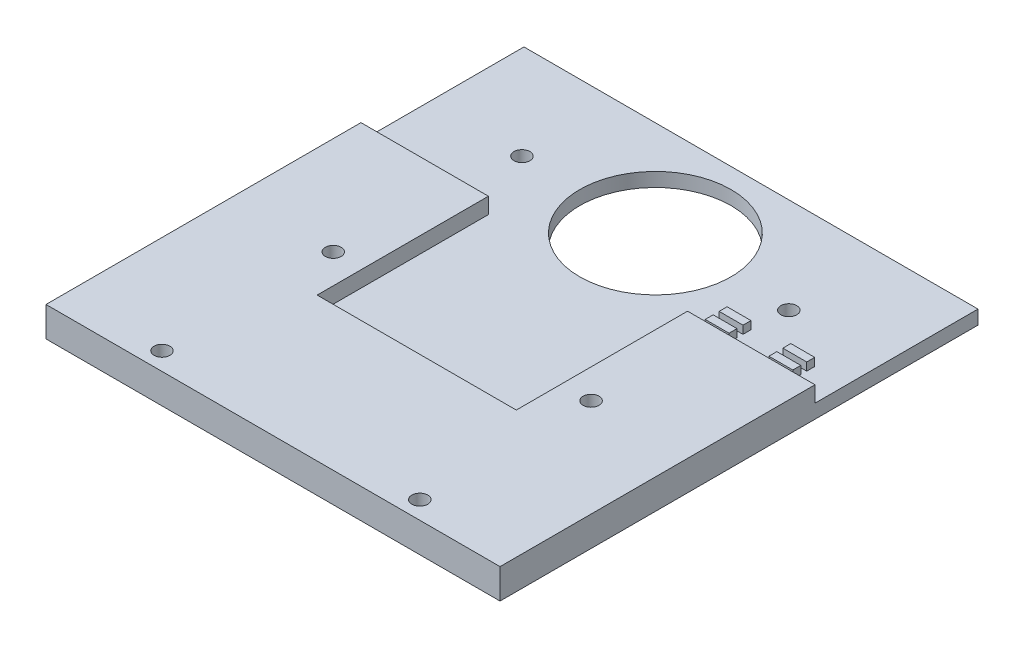
SolidWorks part; units mm, degrees
ref_plane "Ebene vorne" through (0, 0, 0) normal (0, 0, 1) x (1, 0, 0)
ref_plane "Ebene oben" through (0, 0, 0) normal (0, 1, 0) x (1, 0, 0)
ref_plane "Ebene rechts" through (0, 0, 0) normal (1, 0, 0) x (0, 0, -1)
sketch "Skizze1" plane through (0, 0, 0) normal (0, 1, 0) x (1, 0, 0)
  line L1 (0, 0) -> (57, 0)
  line L2 (0, 0) -> (0, 60)
  line L3 (0, 60) -> (57, 60)
  line L4 (57, 0) -> (57, 60)
  dimension "D1" = 57
  dimension "D2" = 60
extrude "Aufsatz-Linear austragen1" add sketch "Skizze1" against normal blind 1.75
sketch "Skizze3" plane through (0, 0, 0) normal (0, 1, 0) x (1, 0, 0)
  line L0 (57, 60) -> (0, 60) construction
  line L2 (57, 0) -> (57, 60) construction
  circle A0 centre (28.5, 48) radius 9.4954
  dimension "D1" = 12
  dimension "D2" = 28.5
extrude "Schnitt-Linear austragen1" cut sketch "Skizze3" against normal blind 2
sketch "Skizze4" plane through (0, 0, 0) normal (0, 1, 0) x (1, 0, 0)
  line L0 (0, 60) -> (0, 0) construction
  line L1 (57, 0) -> (0, 0)
  line L2 (57, 0) -> (57, 39.5386)
  line L3 (57, 39.5386) -> (0, 39.5386)
  line L4 (0, 0) -> (0, 39.5386)
extrude "Aufsatz-Linear austragen2" add sketch "Skizze4" along normal blind 2
sketch "Skizze5" plane through (0, 2, 0) normal (0, 1, 0) x (1, 0, 0)
  circle A0 centre (12.3153, 23.7449) radius 1
  circle A1 centre (12.3153, 2.2449) radius 1
  dimension "D1" = 2
  dimension "D2" = 2
extrude "Schnitt-Linear austragen2" cut sketch "Skizze5" against normal blind 4
ref_plane "Ebene1" through (28.5, 0, 0) normal (-1, 0, 0) x (0, 0, 1)
mirror "Spiegeln1" about plane through (28.5, 0, 0) normal (-1, 0, 0) of "Schnitt-Linear austragen2"
sketch "Skizze10" plane through (0, 0, 0) normal (0, 1, 0) x (1, 0, 0)
  line L1 (57, 60) -> (0, 60) construction
  line L2 (57, 39.5386) -> (57, 60) construction
  line L3 (0, 60) -> (0, 39.5386) construction
  circle A0 centre (45.25, 48) radius 1
  circle A1 centre (11.75, 48) radius 1
  dimension "D1" = 12
  dimension "D2" = 12
  dimension "D3" = 11.75
  dimension "D4" = 11.75
extrude "Schnitt-Linear austragen3" cut sketch "Skizze10" against normal blind 2
sketch "Skizze13" plane through (0, 0, 0) normal (0, 1, 0) x (1, 0, 0)
  line L0 (53, 42.5) -> (50, 42.5)
  line L1 (50, 42.5) -> (50, 43.5)
  line L2 (50, 43.5) -> (53, 43.5)
  line L5 (45, 42.5) -> (45, 43.5)
  line L6 (45, 43.5) -> (42, 43.5)
  line L7 (42, 43.5) -> (42, 42.5)
  line L8 (42, 42.5) -> (45, 42.5)
  line L9 (53, 40.75) -> (50, 40.75)
  line L10 (50, 40.75) -> (50, 41.75)
  line L11 (50, 41.75) -> (53, 41.75)
  line L12 (53, 41.75) -> (53, 40.75)
  line L14 (45, 41.75) -> (42, 41.75)
  line L15 (42, 41.75) -> (42, 40.75)
  line L16 (42, 40.75) -> (45, 40.75)
  line L17 (45, 40.75) -> (45, 41.75)
  line L18 (57, 60) -> (0, 60) construction
  line L19 (57, 39.5386) -> (57, 60) construction
  line L20 (53, 42.5) -> (53, 43.5)
  dimension "D1" = 0.75
  dimension "D2" = 1
  dimension "D3" = 1
  dimension "D4" = 0.75
  dimension "D5" = 16.5
  dimension "D6" = 16.5
  dimension "D7" = 4
  dimension "D8" = 1
  dimension "D9" = 3
  dimension "D10" = 1
  dimension "D11" = 3
  dimension "D12" = 3
  dimension "D13" = 16.5
extrude "Aufsatz-Linear austragen6" add sketch "Skizze13" along normal blind 1
ref_plane "Ebene2" through (0, 0, -22) normal (0, 0, -1) x (-1, 0, 0)
sketch "Skizze14" plane through (0, 2, 0) normal (0, 1, 0) x (1, 0, 0)
  line L0 (16, 18.0386) -> (16, 39.5386)
  line L1 (16, 39.5386) -> (41, 39.5386)
  line L2 (41, 39.5386) -> (41, 18.0386)
  line L3 (41, 18.0386) -> (16, 18.0386)
  line L5 (17, 38.5386) -> (17, 19.0386) construction
  line L6 (17, 19.0386) -> (40, 19.0386) construction
  point P5 (16.3675, 18.1919)
  dimension "D1" = 25
  dimension "D2" = 21.5
  dimension "D3" = 1
  dimension "D4" = 1
extrude "Schnitt-Linear austragen4" cut sketch "Skizze14" against normal blind 2
